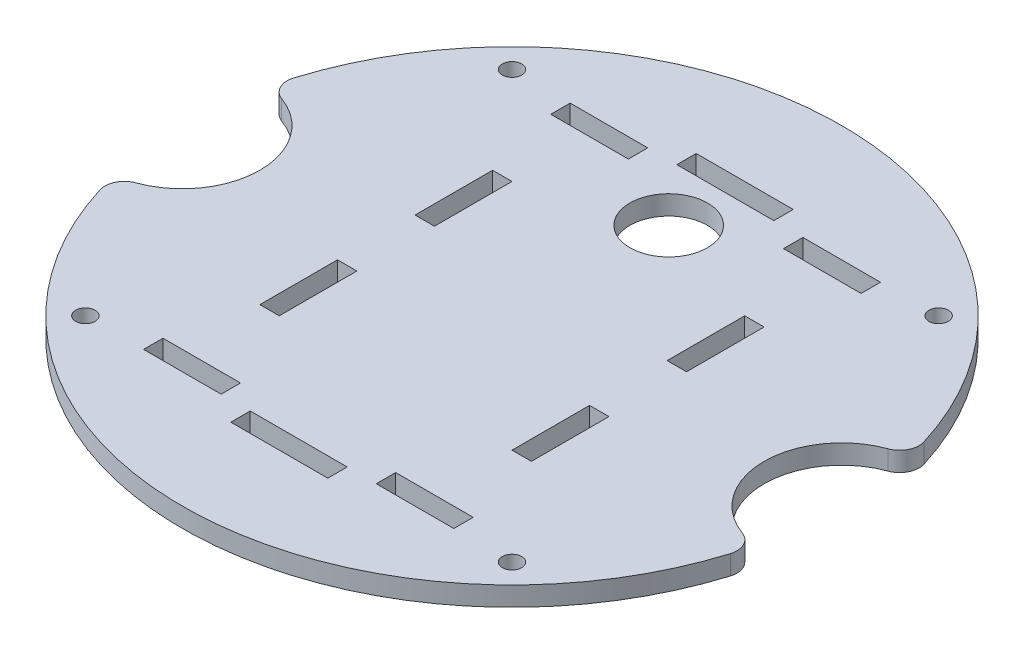
SolidWorks part; units mm, degrees
material "Pine"
ref_plane "Front Plane" through (0, 0, 0) normal (0, 0, 1) x (1, 0, 0)
ref_plane "Top Plane" through (0, 0, 0) normal (0, 1, 0) x (1, 0, 0)
ref_plane "Right Plane" through (0, 0, 0) normal (1, 0, 0) x (0, 0, -1)
sketch "Sketch1" plane through (0, 0, 0) normal (0, 1, 0) x (1, 0, 0)
  line L0 (0, 0) -> (0, 123.9148) construction
  line L1 (0, 0) -> (144.4711, 0) construction
  line L2 (-50.8, 63.5) -> (-25.4, 63.5)
  line L3 (-50.8, 63.5) -> (-50.8, 69.85)
  line L4 (-50.8, 69.85) -> (-25.4, 69.85)
  line L5 (-25.4, 63.5) -> (-25.4, 69.85)
  line L6 (25.4, 63.5) -> (25.4, 69.85)
  line L7 (50.8, 69.85) -> (25.4, 69.85)
  line L8 (50.8, 63.5) -> (50.8, 69.85)
  line L9 (50.8, 63.5) -> (25.4, 63.5)
  line L10 (-25.4, -63.5) -> (-25.4, -69.85)
  line L11 (-50.8, -63.5) -> (-25.4, -63.5)
  line L12 (-50.8, -63.5) -> (-50.8, -69.85)
  line L13 (-50.8, -69.85) -> (-25.4, -69.85)
  line L14 (50.8, -63.5) -> (50.8, -69.85)
  line L15 (50.8, -69.85) -> (25.4, -69.85)
  line L16 (25.4, -63.5) -> (25.4, -69.85)
  line L17 (50.8, -63.5) -> (25.4, -63.5)
  line L18 (38.1, -38.1) -> (44.45, -38.1)
  line L19 (38.1, 38.1) -> (44.45, 38.1)
  line L20 (38.1, 38.1) -> (38.1, 12.7)
  line L21 (38.1, 12.7) -> (44.45, 12.7)
  line L22 (44.45, 38.1) -> (44.45, 12.7)
  line L23 (38.1, -38.1) -> (38.1, -12.7)
  line L24 (38.1, -12.7) -> (44.45, -12.7)
  line L25 (44.45, -38.1) -> (44.45, -12.7)
  line L26 (-38.1, -38.1) -> (-44.45, -38.1)
  line L27 (-44.45, -38.1) -> (-44.45, -12.7)
  line L28 (-38.1, -38.1) -> (-38.1, -12.7)
  line L29 (-38.1, -12.7) -> (-44.45, -12.7)
  line L30 (-38.1, 12.7) -> (-44.45, 12.7)
  line L31 (-38.1, 38.1) -> (-38.1, 12.7)
  line L32 (-38.1, 38.1) -> (-44.45, 38.1)
  line L33 (-44.45, 38.1) -> (-44.45, 12.7)
  line L34 (-15.875, 69.85) -> (-15.875, 76.2)
  line L35 (15.875, -69.85) -> (-15.875, -69.85)
  line L36 (15.875, -69.85) -> (15.875, -76.2)
  line L37 (15.875, -76.2) -> (-15.875, -76.2)
  line L38 (-15.875, -69.85) -> (-15.875, -76.2)
  line L39 (15.875, -69.85) -> (-15.875, -76.2) construction
  line L40 (15.875, -76.2) -> (-15.875, -69.85) construction
  line L41 (15.875, 76.2) -> (-15.875, 76.2)
  line L42 (15.875, 69.85) -> (15.875, 76.2)
  line L43 (15.875, 69.85) -> (-15.875, 69.85)
  arc A0 (-103.1875, -31.7103) -> (103.1875, -31.7103) centre (0, 0) ccw
  circle A1 centre (0, 51.308) radius 12.7
  arc A2 (-99.2841, -23.876) -> (-99.2841, 23.876) centre (-107.95, 0) ccw
  arc A3 (-99.2841, 23.876) -> (-103.1875, 31.7103) centre (-97.1176, 29.845) cw
  arc A4 (-99.2841, -23.876) -> (-103.1875, -31.7103) centre (-97.1176, -29.845) ccw
  arc A5 (99.2841, -23.876) -> (103.1875, -31.7103) centre (97.1176, -29.845) cw
  arc A6 (99.2841, -23.876) -> (99.2841, 23.876) centre (107.95, 0) cw
  arc A7 (99.2841, 23.876) -> (103.1875, 31.7103) centre (97.1176, 29.845) ccw
  arc A8 (103.1875, 31.7103) -> (-103.1875, 31.7103) centre (0, 0) ccw
  arc A9 (-18.5066, 54.929) -> (-18.5273, 53.3918) centre (10.0451, 53.7772) ccw construction
  arc A11 (4.1885, 48.7609) -> (5.6834, 48.4758) centre (5.3398, 50.7358) ccw construction
  point P52 (0, -73.025)
  point P61 (-18.5273, 54.1605)
  point P66 (4.9116, 48.4903)
  dimension "D1" = 215.9
  dimension "D10" = 25.4
  dimension "D12" = 50.8
  dimension "D13" = 6.35
  dimension "D14" = 6.35
  dimension "D11" = 51.308
  dimension "D2" = 25.4
  dimension "D3" = 25.4
  dimension "D4" = 6.35
  dimension "D5" = 63.5
  dimension "D6" = 6.35
  dimension "D7" = 25.4
  dimension "D8" = 12.7
  dimension "D9" = 38.1
  dimension "D15" = 31.75
  dimension "D16" = 6.35
extrude "Boss-Extrude1" add sketch "Sketch1" along normal blind 6.35
sketch "Sketch2" plane through (0, 0, 0) normal (0, -1, 0) x (1, 0, 0)
  line L0 (0, 0) -> (0, 99.3828) construction
  line L1 (0, 0) -> (-150.0844, 0) construction
  circle A0 centre (-69.85, 69.85) radius 3.175
  circle A1 centre (69.85, 69.85) radius 3.175
  circle A2 centre (69.85, -69.85) radius 3.175
  circle A3 centre (-69.85, -69.85) radius 3.175
  dimension "D1" = 6.35
extrude "Cut-Extrude1" cut sketch "Sketch2" against normal up to surface (6.35 mm away) up to face at (0, 6.35, 73.025)
